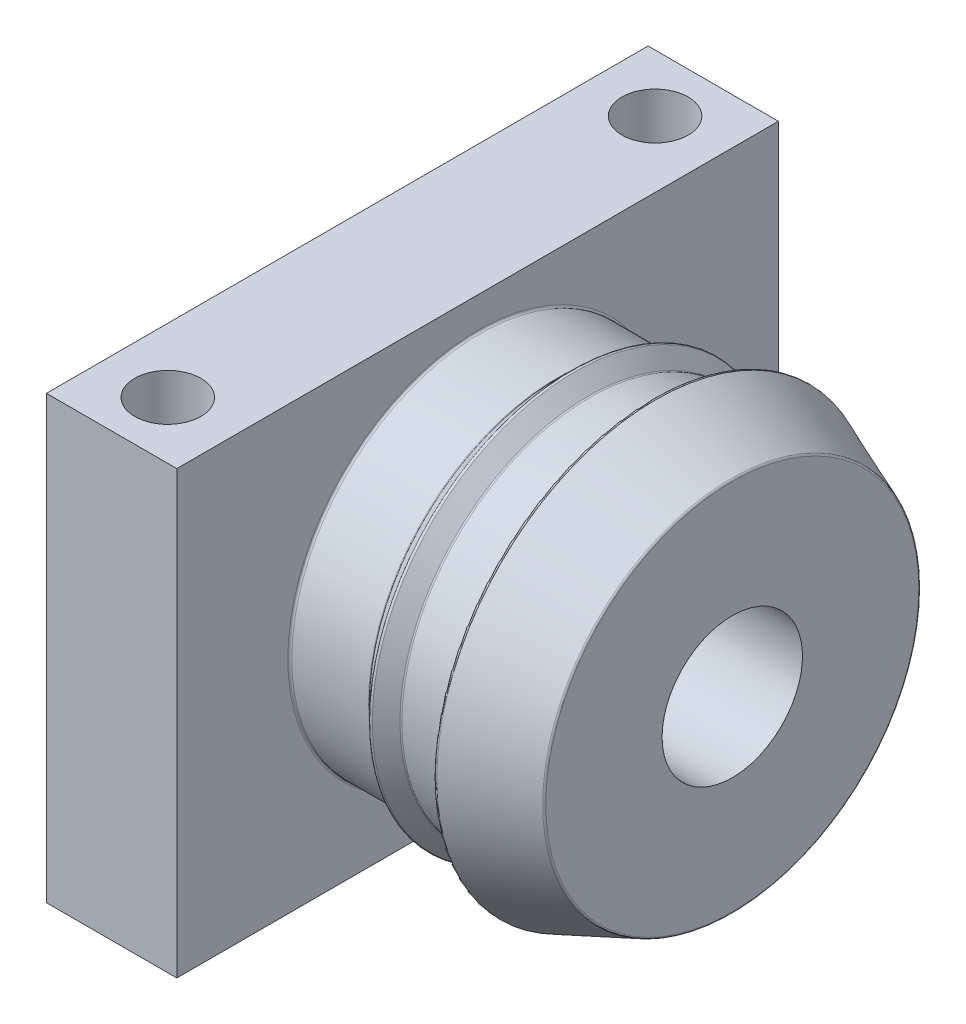
SolidWorks part; units mm, degrees
note: The reader was unsure of these and kept them because the rebuilt part matched: shared geometry of "Sketch2<3>", "Sketch2<4>", "Sketch2<5>", "Sketch2<6>".
ref_plane "Front Plane" through (0, 0, 0) normal (0, 0, 1) x (1, 0, 0)
ref_plane "Top Plane" through (0, 0, 0) normal (0, 1, 0) x (1, 0, 0)
ref_plane "Right Plane" through (0, 0, 0) normal (1, 0, 0) x (0, 0, -1)
sketch "Sketch1" plane through (0, 0, 0) normal (0, 1, 0) x (1, 0, 0)
  line L0 (0, 0) -> (-12.7, 0)
  line L1 (0, 0) -> (0, 9.365)
  line L2 (0, 9.365) -> (-3.97, 10.955)
  line L3 (-3.97, 10.955) -> (-3.97, 9.365)
  line L4 (0, 9.365) -> (-19.3321, 9.365) construction
  line L5 (-3.97, 9.365) -> (-7.15, 9.365)
  line L6 (-7.15, 9.365) -> (-7.94, 10.155)
  line L7 (-7.94, 10.155) -> (-8.73, 9.365)
  line L8 (-8.73, 9.365) -> (-12.7, 9.365)
  line L9 (-12.7, 9.365) -> (-12.7, 0)
  dimension "D1" = 12.7
  dimension "D2" = 9.365
  dimension "D3" = 1.59
  dimension "D4" = 3.97
  dimension "D5" = 7.94
  dimension "D6" = 0.79
revolve "Revolve1" add sketch "Sketch1" angle 360 about L0
sketch "Sketch2" plane through (-12.7, 0, 0) normal (-1, 0, 0) x (0, 0, 1)
  line L0 (0.92, 2.735) -> (0.92, -1.615)
  line L1 (-8.59, 6.425) -> (8.59, 6.425) construction
  line L2 (-8.59, 6.425) -> (-8.59, -6.425) construction
  line L3 (-8.59, -6.425) -> (8.59, -6.425) construction
  line L4 (8.59, 6.425) -> (8.59, -6.425) construction
  line L5 (-8.59, 6.425) -> (8.59, -6.425) construction
  line L6 (-8.59, -6.425) -> (8.59, 6.425) construction
  line L7 (0.92, -1.615) -> (-1.54, -1.615)
  line L8 (-1.54, -1.615) -> (-1.54, 2.735)
  line L9 (-1.54, 2.735) -> (0.92, 2.735)
  line L10 (0, 6.425) -> (0, -6.425) construction
  line L11 (15, 11) -> (-15, 11)
  line L12 (15, 11) -> (15, -11)
  line L13 (15, -11) -> (-15, -11)
  line L14 (-15, 11) -> (-15, -11)
  line L15 (15, 11) -> (-15, -11) construction
  line L16 (15, -11) -> (-15, 11) construction
  line L18 (-8.59, -6.425) -> (8.59, -6.425)
  line L19 (-8.59, -6.425) -> (-8.59, -4.625)
  line L20 (-8.59, -4.625) -> (8.59, -4.625)
  line L21 (8.59, -6.425) -> (8.59, -4.625)
  line L22 (-8.59, -6.425) -> (8.59, -4.625) construction
  line L23 (-8.59, -4.625) -> (8.59, -6.425) construction
  line L28 (-9.29, 6.625) -> (9.29, 6.625)
  line L29 (-9.29, 6.625) -> (-9.29, -7.425)
  line L30 (-9.29, -7.425) -> (9.29, -7.425)
  line L31 (9.29, 6.625) -> (9.29, -7.425)
  line L32 (-9.29, 6.625) -> (9.29, -7.425) construction
  line L33 (-9.29, -7.425) -> (9.29, 6.625) construction
  circle A0 centre (-6.19, 3.935) radius 0.9
  circle A1 centre (6.19, 3.935) radius 0.9
  circle A2 centre (0, 0) radius 3.5
  point P0 (0, 0)
  point P8 (0, 0)
  point P25 (0, -5.525)
  point P35 (0, -0.4)
  circle M5 centre (0, 0) radius 9.365
  dimension "D9" = 1.8
  dimension "D10" = 2.49
  dimension "D11" = 2.4
  dimension "D12" = 7
  dimension "D1" = 12.85
  dimension "D2" = 17.18
  dimension "D3" = 7.67
  dimension "D4" = 3.69
  dimension "D5" = 2.46
  dimension "D6" = 4.35
  dimension "D7" = 22
  dimension "D8" = 30
  dimension "D13" = 1.8
  dimension "D14" = 0.7
  dimension "D15" = 0.7
  dimension "D16" = 0.2
  dimension "D17" = 1
extrude "Boss-Extrude1" add sketch "Sketch2" along normal blind 1.5
extrude "Boss-Extrude2" add sketch "Sketch2<3>" along normal offset from surface (2 mm away) 0.5 contours L20 L18 M5 | L18 L21 L20 M5 | L20 L19 L18 M5 up to face at (-14.2, 0, 0) offset beyond the face yes
sketch "Sketch2<3>" plane through (-12.7, 0, 0) normal (-1, 0, 0) x (0, 0, 1) same geometry as "Sketch2"
extrude "Boss-Extrude3" add sketch "Sketch2<4>" along normal offset from surface (5 mm away) 3.5 contours A1 | A0 up to face at (-14.2, -5.525, 0) offset beyond the face yes
sketch "Sketch2<4>" plane through (-12.7, 0, 0) normal (-1, 0, 0) x (0, 0, 1) same geometry as "Sketch2"
extrude "Cut-Extrude1" cut sketch "Sketch2<5>" against normal through all contours A2 L8 L9 L0 L7 | L9 L8 L7 L0
sketch "Sketch2<5>" plane through (-12.7, 0, 0) normal (-1, 0, 0) x (0, 0, 1) same geometry as "Sketch2"
extrude "Boss-Extrude4" add sketch "Sketch2<6>" along normal offset from surface (6.5 mm away) 5 contours L11 L14 L13 L12 L28 L31 L30 L29 M5 | L30 M5 | L31 M5 | L29 M5 | L28 M5
sketch "Sketch2<6>" plane through (-12.7, 0, 0) normal (-1, 0, 0) x (0, 0, 1) same geometry as "Sketch2"
fillet "Fillet1" radius 0.1 7 edges at (-12.7, 0, 9.365) (-8.73, 0, -9.365) (-7.15, 0, -9.365) (-7.94, 0, -10.155) (-3.97, 0, -9.365) (-3.97, 0, -10.955) (0, 0, -9.365)
fillet "Fillet4" radius 0.2 2 edges at (-17.7, 3.935, -5.29) (-17.7, 3.935, 7.09)
fillet "Fillet5" radius 0.2 4 edges at (-14.7, -5.525, -8.59) (-14.7, -6.425, 0) (-14.7, -5.525, 8.59) (-14.7, -4.625, 0)
ref_plane "Plane1" through (0, 3.5, 0) normal (0, -1, 0) x (-1, 0, 0)
sketch "Sketch4" plane through (0, 3.5, 0) normal (0, -1, 0) x (-1, 0, 0)
  line L0 (16, 9.3) -> (16, 15) construction
  line L2 (19.2, 15) -> (12.7, 15) construction
  line L3 (12.7, -15) -> (12.7, 15) construction
  circle A0 centre (16, 12.15) radius 1.65
  point P4 (16, 10.0698)
  point P8 (0, 0)
  point P10 (16, 12.15)
  dimension "D1" = 3.3
  dimension "D2" = 3.3
  dimension "D3" = 5.7
extrude "Cut-Extrude2" cut sketch "Sketch4" against normal through all and the other way through all
ref_plane "Plane2" through (0, 0, 0) normal (0, 0, -1) x (-1, 0, 0)
mirror "Mirror1" about plane through (0, 0, 0) normal (0, 0, -1) of "Cut-Extrude2"
sketch "Sketch5" plane through (0, 0, 0) normal (0, 0, -1) x (-1, 0, 0)
  line L0 (17.9, -11) -> (17.9, -9.8342)
  line L1 (19.2, -11) -> (12.7, -11) construction
  line L2 (17.9, -9.8342) -> (15.4, -11)
  line L3 (15.4, -11) -> (17.9, -11)
  line L4 (19.2, 11) -> (19.2, -11) construction
  line L5 (14.35, -11) -> (17.65, -11) construction
  dimension "D1" = 1.3
  dimension "D2" = 2.5
  dimension "D3" = 65
extrude "Cut-Extrude3" cut sketch "Sketch5" against normal blind 7 and the other way blind 7
sketch "Sketch6" plane through (-19.2, 0, 0) normal (-1, 0, 0) x (0, 0, 1)
  line L0 (-9.29, 6.625) -> (-9.29, -7.425) construction
  line L1 (-10.79, 7.625) -> (10.29, 7.625)
  line L2 (-10.79, 7.625) -> (-10.79, -8.425)
  line L3 (-10.79, -8.425) -> (10.29, -8.425)
  line L4 (10.29, 7.625) -> (10.29, -8.425)
  line L5 (-10.79, 7.625) -> (10.29, -8.425) construction
  line L6 (-10.79, -8.425) -> (10.29, 7.625) construction
  line L7 (9.29, 6.625) -> (-9.29, 6.625) construction
  line L8 (9.29, 6.625) -> (9.29, -7.425) construction
  line L9 (9.29, -7.425) -> (-9.29, -7.425) construction
  point P4 (-0.25, -0.4)
  dimension "D1" = 1.5
  dimension "D2" = 1
  dimension "D3" = 1
  dimension "D4" = 1
sweep "Cut-Sweep1" cut path "Sketch6" circular profile diameter 1.2 parameters "D3"=1.2
fillet "Fillet6" radius 0.2 2 edges at (-14.2, 3.935, -5.29) (-14.2, 3.935, 7.09)
equation "\"WallThick\"= 1.2'thickness of wall for printer"
equation "\"D3@Sketch4\"=\"WallThick\"*2+\"dHole\""
equation "\"dHole\"= 3.3'diameter of screw hole"
